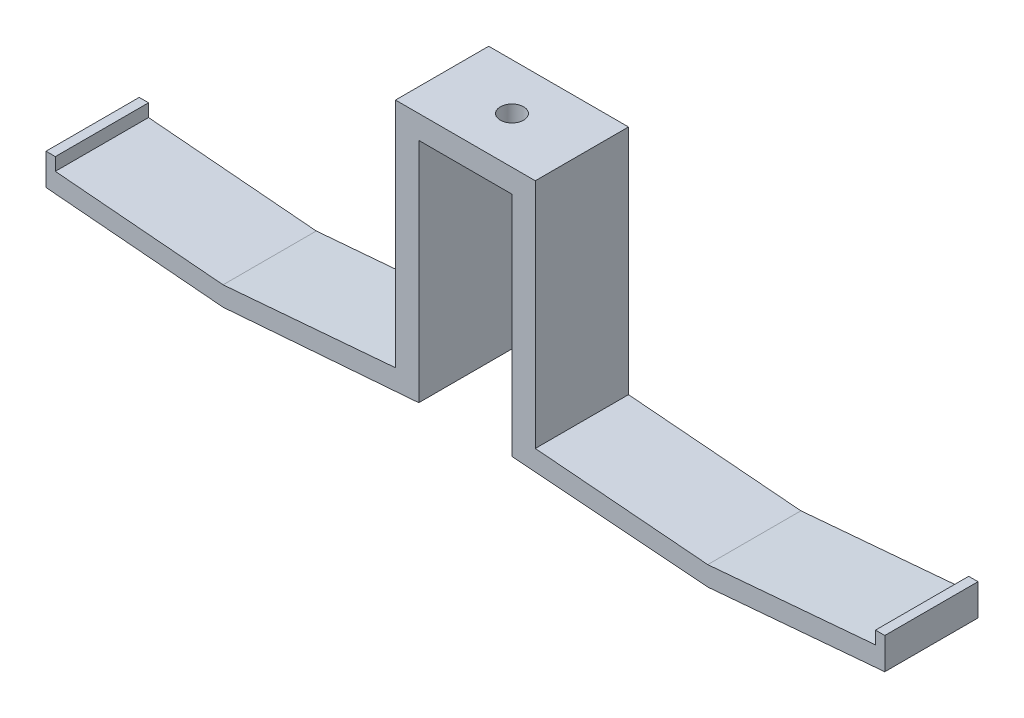
SolidWorks part; units mm, degrees
material "Nylon 6/10"
ref_plane "Front Plane" through (0, 0, 0) normal (0, 0, 1) x (1, 0, 0)
ref_plane "Top Plane" through (0, 0, 0) normal (0, 1, 0) x (1, 0, 0)
ref_plane "Right Plane" through (0, 0, 0) normal (1, 0, 0) x (0, 0, -1)
sketch "Sketch2" plane through (0, 0, 0) normal (0, 0, 1) x (1, 0, 0)
  line L1 (12.7, 0) -> (12.7, -61.918)
  line L2 (12.7, -61.918) -> (66.04, -66.0514)
  line L3 (66.04, -66.0514) -> (114.3, -61.918)
  line L4 (114.3, -61.918) -> (114.3, -53.3514)
  line L5 (111.76, -53.3514) -> (111.76, -56.838)
  line L6 (111.76, -56.838) -> (66.04, -60.7538)
  line L19 (114.3, -53.3514) -> (111.76, -53.3514)
  line L20 (0, 125.2351) -> (0, -75.9356) construction
  line L21 (12.7, 0) -> (-12.7, 0)
  line L22 (0, 0) -> (0, 6.35)
  line L23 (19.05, 6.35) -> (-19.05, 6.35)
  line L24 (19.05, 6.35) -> (19.05, 0)
  line L25 (19.05, 0) -> (19.05, -56.838)
  line L26 (19.05, -56.838) -> (66.04, -60.7538)
  line L27 (-19.05, 0) -> (-19.05, -56.838)
  line L28 (-19.05, 6.35) -> (-19.05, 0)
  line L29 (-12.7, 0) -> (-12.7, -61.918)
  line L30 (-12.7, -61.918) -> (-66.04, -66.0514)
  line L31 (-66.04, -66.0514) -> (-114.3, -61.918)
  line L32 (-114.3, -61.918) -> (-114.3, -53.3514)
  line L33 (-114.3, -53.3514) -> (-111.76, -53.3514)
  line L34 (-111.76, -53.3514) -> (-111.76, -56.838)
  line L35 (-111.76, -56.838) -> (-66.04, -60.7538)
  line L36 (-19.05, -56.838) -> (-66.04, -60.7538)
  dimension "D1" = 19.05
  dimension "D2" = 12.7
  dimension "D3" = 56.838
  dimension "D4" = 3.9158
  dimension "D5" = 61.918
  dimension "D6" = 2.54
  dimension "D7" = 45.72
  dimension "D8" = 46.99
  dimension "D9" = 12.7
  dimension "D10" = 6.35
extrude "Boss-Extrude1" add sketch "Sketch2" along normal blind 25.4 contours L26 L25 L24 L23 L22 L21 L1 L2 L3 L4 L19 L5 L6 | L27 L36 L35 L34 L33 L32 L31 L30 L29 L21 L22 L23 L28 region at (6.35, 1.353, 0) region at (-6.35, 1.353, 0)
sketch "Sketch3" plane through (0, 6.35, 0) normal (0, 1, 0) x (1, 0, 0)
  line L0 (19.05, -12.7) -> (-19.05, -12.7) construction
  line L1 (19.05, -25.4) -> (19.05, 0) construction
  line L2 (-19.05, -25.4) -> (-19.05, 0) construction
  circle A0 centre (0, -12.7) radius 3.175
  dimension "D1" = 6.35
extrude "Cut-Extrude1" cut sketch "Sketch3" against normal up to next
